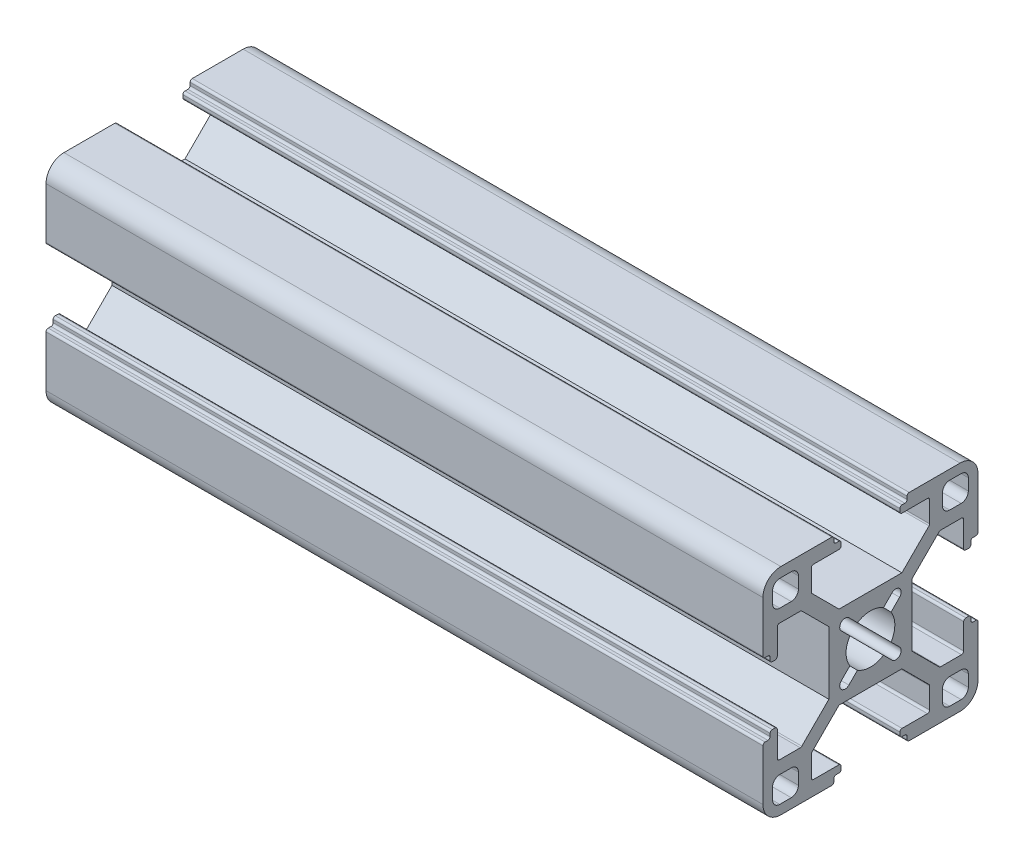
SolidWorks part; units mm, degrees
material "A6063"
ref_plane "Front Plane" through (0, 0, 0) normal (0, 0, 1) x (1, 0, 0)
ref_plane "Top Plane" through (0, 0, 0) normal (0, 1, 0) x (1, 0, 0)
ref_plane "Right Plane" through (0, 0, 0) normal (1, 0, 0) x (0, 0, -1)
ref_axis "Axis_X" through (-58.3, 0, 0) along (1, 0, 0)
ref_axis "Axis_Y" through (0, 38.5, 0) along (0, -1, 0)
ref_axis "Axis_Z" through (0, 0, -4.5) along (0, 0, 1)
sketch "Sketch2" plane through (0, 0, 0) normal (1, 0, 0) x (0, 0, -1)
  line L1 (-15, 15) -> (15, 15)
  line L2 (-15, 15) -> (-15, -15)
  line L3 (-15, -15) -> (15, -15)
  line L4 (15, 15) -> (15, -15)
  line L5 (-15, 15) -> (15, -15) construction
  line L6 (-15, -15) -> (15, 15) construction
  point P0 (0, 0)
  dimension "D1" = 30
  dimension "D2" = 30
extrude "Boss-Extrude1" add sketch "Sketch2" along normal blind 100
sketch "Sketch5" plane through (100, 0, 0) normal (1, 0, 0) x (0, 0, -1)
  circle A0 centre (0, 0) radius 3.4
  dimension "D1" = 6.8
extrude "Cut-Extrude2" cut sketch "Sketch5" against normal through all
sketch "Sketch4" plane through (100, 0, 0) normal (1, 0, 0) x (0, 0, -1)
  line L0 (-4.3858, -5.8) -> (4.3858, -5.8)
  line L1 (4.3858, -5.8) -> (8.1621, -9.5763)
  line L2 (8.25, -9.7885) -> (8.25, -13)
  line L3 (8.25, -13) -> (4.1, -13)
  line L4 (4.1, -13) -> (4.1, -14)
  line L5 (4.1, -14) -> (5.1, -14)
  line L6 (5.1, -14) -> (5.1, -15)
  line L7 (-15, -15) -> (15, -15) construction
  line L8 (5.1, -15) -> (-5.1, -15)
  line L9 (-5.1, -15) -> (-5.1, -14)
  line L10 (-5.1, -14) -> (-4.1, -14)
  line L11 (-4.1, -14) -> (-4.1, -13)
  line L12 (-4.1, -13) -> (-8.25, -13)
  line L13 (-8.25, -13) -> (-8.25, -9.7885)
  line L14 (-8.1621, -9.5763) -> (-4.3858, -5.8)
  line L16 (-4.1, -13) -> (4.1, -13) construction
  line L17 (0, -14) -> (0, -15) construction
  line L18 (-4.1, -14) -> (4.1, -14) construction
  line L19 (0, -5.8) -> (0, -13) construction
  line L20 (0, -13) -> (0, -14) construction
  line L21 (15, -15) -> (15, 15) construction
  line L22 (11.05, -10.05) -> (12.65, -10.05)
  line L23 (10.05, -11.05) -> (10.05, -12.65)
  line L24 (11.05, -13.65) -> (12.65, -13.65)
  line L25 (13.65, -11.05) -> (13.65, -12.65)
  line L26 (10.05, -10.05) -> (13.65, -13.65) construction
  line L27 (10.05, -13.65) -> (13.65, -10.05) construction
  line L28 (0, 0) -> (3.5355, -3.5355) construction
  line L29 (15, -15) -> (15, 15) construction
  line L30 (4.0659, -3.0052) -> (2.8753, -1.8146)
  line L31 (3.0052, -4.0659) -> (1.8146, -2.8753)
  arc A0 (12.65, -13.65) -> (13.65, -12.65) centre (12.65, -12.65) ccw
  arc A1 (11.05, -13.65) -> (10.05, -12.65) centre (11.05, -12.65) cw
  arc A2 (10.05, -11.05) -> (11.05, -10.05) centre (11.05, -11.05) cw
  arc A3 (12.65, -10.05) -> (13.65, -11.05) centre (12.65, -11.05) cw
  arc A4 (3.0052, -4.0659) -> (4.0659, -3.0052) centre (3.5355, -3.5355) ccw
  circle A5 centre (0, 0) radius 3.4 construction
  arc A6 (1.8146, -2.8753) -> (2.8753, -1.8146) centre (0, 0) ccw
  arc A7 (-8.25, -9.7885) -> (-8.1621, -9.5763) centre (-7.95, -9.7885) cw
  arc A8 (8.25, -9.7885) -> (8.1621, -9.5763) centre (7.95, -9.7885) ccw
  point P18 (11.85, -11.85)
  point P47 (-8.25, -9.6642)
  point P55 (8.25, -9.6642)
  dimension "D11" = 1
  dimension "D14" = 1.5
  dimension "D2" = 0.3
  dimension "D1" = 9.2
  dimension "D3" = 1
  dimension "D4" = 8.2
  dimension "D5" = 10.2
  dimension "D6" = 16.5
  dimension "D7" = 2
  dimension "D8" = 1.35
  dimension "D9" = 1.35
  dimension "D10" = 3.6
  dimension "D12" = 45
  dimension "D13" = 5
  dimension "D15" = 5.4237
extrude "Cut-Extrude1" cut sketch "Sketch4" against normal through all
fillet "Fillet1" radius 2.5 1 edges at (50, -15, -15)
fillet "Fillet2" radius 0.3 10 edges at (50, -14, -5.1) (50, -15, -5.1) (50, -14, -4.1) (50, -13, -4.1) (50, -13, -8.25) (50, -13, 8.25) (50, -13, 4.1) (50, -14, 4.1) (50, -14, 5.1) (50, -15, 5.1)
pattern_circular "CirPattern1" count 4 over 360 about axis through (0, 0, 0) along (1, 0, 0) of "Cut-Extrude1", "Fillet1", "Fillet2"
equation "\"Factor\"= 1.082532"
